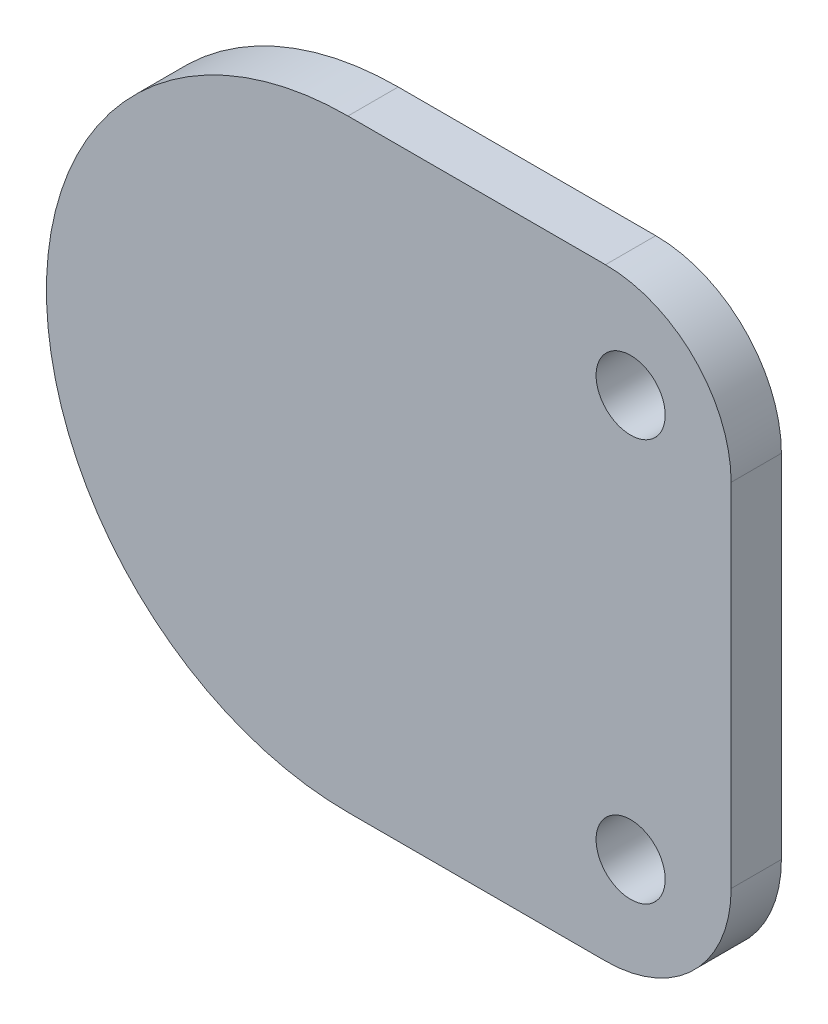
SolidWorks part; units mm, degrees
ref_plane "Front Plane" through (0, 0, 0) normal (0, 0, 1) x (1, 0, 0)
ref_plane "Top Plane" through (0, 0, 0) normal (0, 1, 0) x (1, 0, 0)
ref_plane "Right Plane" through (0, 0, 0) normal (1, 0, 0) x (0, 0, -1)
ref_axis "X-Axis" through (88.99, 0, 0) along (-1, 0, 0)
ref_axis "Y-Axis" through (0, 0, -88.99) along (0, 0, 1)
ref_axis "Z-Axis" through (0, -55, 0) along (0, 1, 0)
sketch "Sketch1" plane through (0, 0, 0) normal (0, 0, 1) x (1, 0, 0)
  line L0 (0, -55) -> (0, 55) construction
  line L1 (88.99, 0) -> (-88.99, 0) construction
  line L6 (0, -24) -> (20.5, -24)
  line L7 (30.5, -14) -> (30.5, 14)
  line L8 (20.5, 24) -> (0, 24)
  circle A2 centre (22.5, -16) radius 2.75
  arc A6 (0, 24) -> (0, -24) centre (0, 0) ccw
  arc A7 (20.5, -24) -> (30.5, -14) centre (20.5, -14) ccw
  arc A8 (30.5, 14) -> (20.5, 24) centre (20.5, 14) ccw
  circle A9 centre (22.5, 16) radius 2.75
  dimension "D1" = 5.5
  dimension "D2" = 5.5
  dimension "D8" = 24
  dimension "D11" = 10
  dimension "D3" = 22.5
  dimension "D4" = 16
  dimension "D5" = 16
  dimension "D6" = 22.5
  dimension "D7" = 30.5
  dimension "D9" = 10
  dimension "D10" = 24
extrude "Boss-Extrude1" add sketch "Sketch1" along normal blind 4
sketch "Sketch2" plane through (0, 0, 0) normal (0, 0, -1) x (-1, 0, 0)
  circle A0 centre (0, 0) radius 16
  circle A1 centre (0, 0) radius 14
  dimension "D1" = 32
  dimension "D2" = 2
extrude "Boss-Extrude2" add sketch "Sketch2" along normal blind 6
